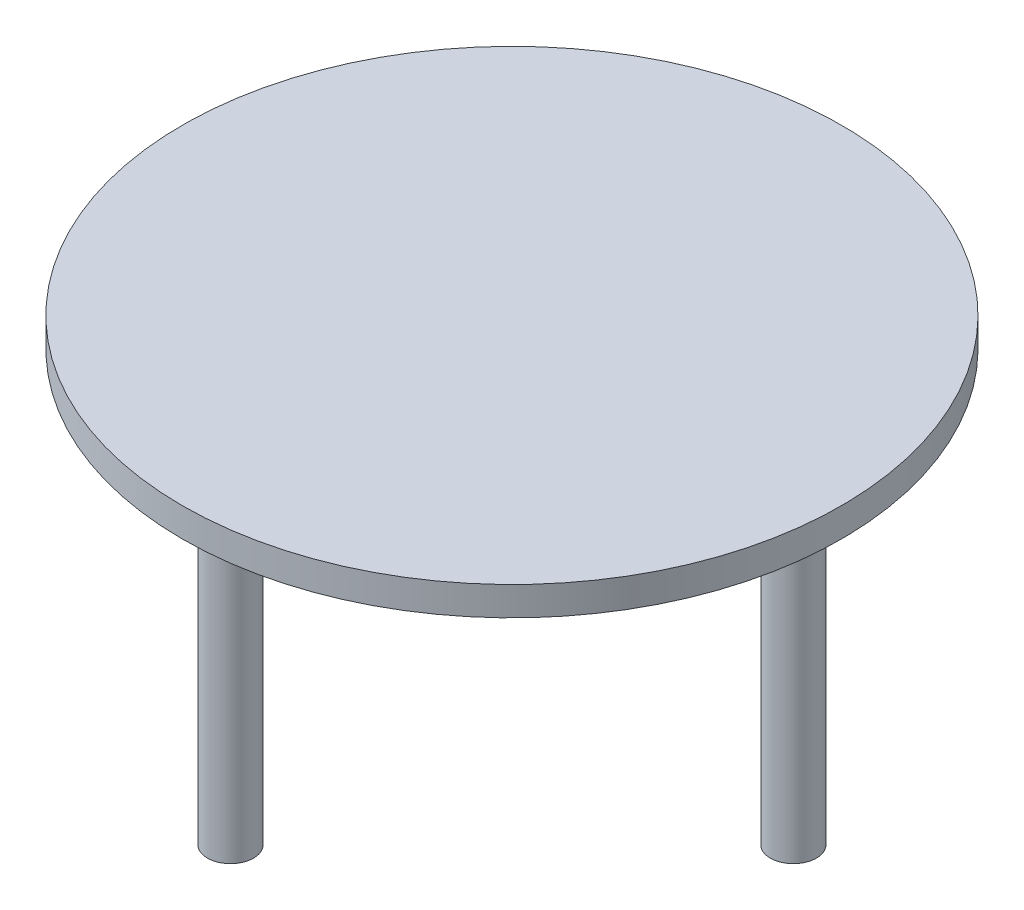
SolidWorks part; units mm, degrees
ref_plane "Ön Düzlem" through (0, 0, 0) normal (0, 0, 1) x (1, 0, 0)
ref_plane "Üst Düzlem" through (0, 0, 0) normal (0, 1, 0) x (1, 0, 0)
ref_plane "Sağ Düzlem" through (0, 0, 0) normal (1, 0, 0) x (0, 0, -1)
sketch "Çizim2" plane through (0, 0, 0) normal (0, 1, 0) x (1, 0, 0)
  circle A0 centre (0, 0) radius 34.2244
  circle A1 centre (0, 29.2244) radius 2.3965
  circle A2 centre (0, -29.2244) radius 2.3965
  circle A3 centre (-29.2244, 0) radius 2.3965
  circle A4 centre (29.2244, 0) radius 2.3965
  circle A5 centre (0, 0) radius 29.2244
  dimension "D1" = 5
extrude "Yükseklik-Ekstrüzyon6" add sketch "Çizim2" along normal blind 3 contours A0 A5 A2 A3 A1 A4 | A2 A5 A4 A1 A3 | A5 A2 | A2 A5 | A4 A5 | A5 A4 | A1 A5 | A5 A1 | A5 A3 | A3 A5 region at (-33.2564, 0, 0) region at (0, 0, -30.2236) region at (0, 0, -28.1898) region at (0, 0, 0) region at (-30.2236, 0, 0) region at (-28.1898, 0, 0) region at (28.1898, 0, 0) region at (30.2236, 0, 0) region at (0, 0, 30.2236) region at (0, 0, 28.1898)
extrude "Yükseklik-Ekstrüzyon7" add sketch "Çizim2<3>" against normal blind 30 contours A5 A3 | A3 A5 | A2 A5 | A5 A2 | A1 A5 | A5 A1 | A4 A5 | A5 A4 region at (0, 0, -30.2236) region at (0, 0, -28.1898) region at (-30.2236, 0, 0) region at (-28.1898, 0, 0) region at (28.1898, 0, 0) region at (30.2236, 0, 0) region at (0, 0, 30.2236) region at (0, 0, 28.1898)
sketch "Çizim2<3>" plane through (0, 0, 0) normal (0, 1, 0) x (1, 0, 0) same geometry as "Çizim2"
